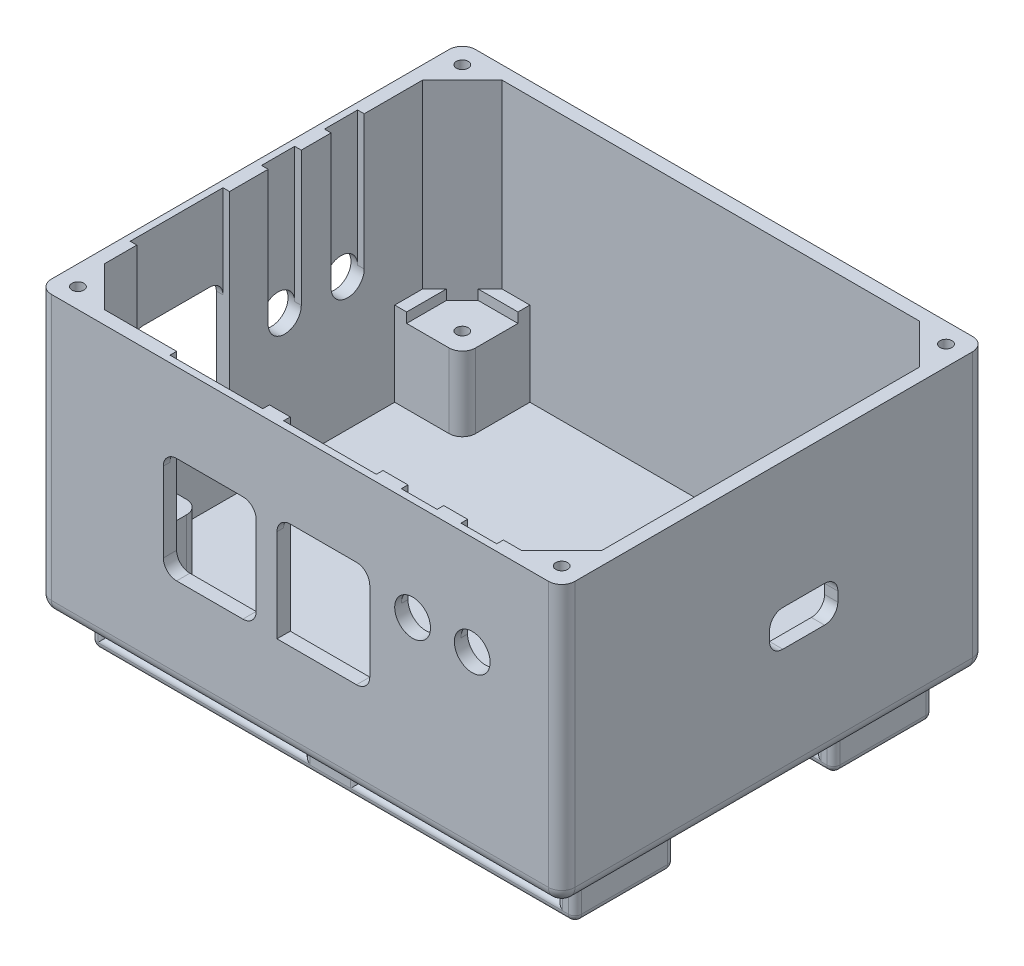
SolidWorks part; units mm, degrees
ref_plane "Front Plane" through (0, 0, 0) normal (0, 0, 1) x (1, 0, 0)
ref_plane "Top Plane" through (0, 0, 0) normal (0, 1, 0) x (1, 0, 0)
ref_plane "Right Plane" through (0, 0, 0) normal (1, 0, 0) x (0, 0, -1)
sketch "Sketch1" plane through (0, 0, 0) normal (0, 1, 0) x (1, 0, 0)
  line L1 (39.5, -32) -> (-39.5, -32)
  line L2 (39.5, -32) -> (39.5, 32)
  line L3 (39.5, 32) -> (-39.5, 32)
  line L4 (-39.5, -32) -> (-39.5, 32)
  line L5 (39.5, -32) -> (-39.5, 32) construction
  line L6 (39.5, 32) -> (-39.5, -32) construction
  point P0 (0, 0)
  dimension "D1" = 79
  dimension "D2" = 64
extrude "Boss-Extrude1" add sketch "Sketch1" along normal blind 2
sketch "Sketch2" plane through (0, 2, 0) normal (0, 1, 0) x (1, 0, 0)
  line L1 (-39.5, 32) -> (39.5, 32)
  line L2 (-39.5, 32) -> (-39.5, -32)
  line L3 (-39.5, -32) -> (39.5, -32)
  line L4 (39.5, 32) -> (39.5, -32)
  line L10 (37.5, -30) -> (-37.5, -30)
  line L14 (37.5, -30) -> (37.5, 30)
  line L15 (37.5, 30) -> (-37.5, 30)
  line L16 (-37.5, -30) -> (-37.5, 30)
  line L17 (37.5, -30) -> (-37.5, 30) construction
  line L18 (37.5, 30) -> (-37.5, -30) construction
  point P6 (0, 0)
  point P7 (0, 0)
  dimension "D1" = 2
  dimension "D2" = 2
extrude "Boss-Extrude2" add sketch "Sketch2" along normal blind 40
sketch "Sketch4" plane through (0, 2, 0) normal (0, 1, 0) x (1, 0, 0)
  line L0 (-37.5, 24) -> (-31.5, 30)
  line L1 (-37.5, 30) -> (-31.5, 30)
  line L2 (-37.5, 30) -> (-37.5, 24)
  line L5 (0, 0) -> (0, 30) construction
  line L6 (37.5, 30) -> (-37.5, 30) construction
  line L10 (0, 0) -> (-37.5, 0) construction
  line L11 (-37.5, 30) -> (-37.5, -30) construction
  line L12 (-37.5, -30) -> (-34.1667, -27.3333) construction
  line L13 (37.5, 30) -> (37.5, 24)
  line L14 (37.5, 30) -> (31.5, 30)
  line L15 (37.5, 24) -> (31.5, 30)
  line L16 (-37.5, -30) -> (-37.5, -24)
  line L17 (-37.5, -30) -> (-31.5, -30)
  line L18 (-37.5, -24) -> (-31.5, -30)
  line L19 (37.5, -30) -> (31.5, -30)
  line L20 (37.5, -24) -> (31.5, -30)
  line L21 (37.5, -30) -> (37.5, -24)
  dimension "D1" = 6
  dimension "D2" = 6
extrude "Boss-Extrude3" add sketch "Sketch4" along normal up to surface (40 mm away) up to face at (0, 42, 0)
sketch "Sketch3" plane through (0, 42, 0) normal (0, 1, 0) x (1, 0, 0)
  line L0 (39.5, 32) -> (-39.5, 32) construction
  line L1 (-39.5, 32) -> (-39.5, -32) construction
  line L3 (-39.5, -32) -> (39.5, -32) construction
  line L4 (39.5, -32) -> (39.5, 32) construction
  circle A0 centre (-36.5, 29) radius 0.9
  circle A1 centre (-36.5, -29) radius 0.9
  circle A2 centre (36.5, -29) radius 0.9
  circle A3 centre (36.5, 29) radius 0.9
  dimension "D1" = 1.8
  dimension "D2" = 3
  dimension "D3" = 3
  dimension "D4" = 1.8
  dimension "D5" = 3
  dimension "D6" = 3
  dimension "D7" = 1.8
  dimension "D8" = 3
  dimension "D9" = 3
  dimension "D10" = 1.8
  dimension "D11" = 3
  dimension "D12" = 3
extrude "Cut-Extrude2" cut sketch "Sketch3" against normal blind 10
sketch "Sketch5" plane through (0, 42, 0) normal (0, 1, 0) x (1, 0, 0)
  line L0 (-31.5, -30) -> (31.5, -30) construction
  line L1 (-20.6111, -30) -> (-6.6111, -30)
  line L2 (-20.6111, -30) -> (-20.6111, -31)
  line L3 (-20.6111, -31) -> (-6.6111, -31)
  line L4 (-6.6111, -30) -> (-6.6111, -31)
  line L5 (-37.5, 24) -> (-37.5, -24) construction
  line L6 (-3.4629, -30) -> (10.5371, -30)
  line L7 (-3.4629, -30) -> (-3.4629, -31)
  line L8 (-3.4629, -31) -> (10.5371, -31)
  line L9 (10.5371, -30) -> (10.5371, -31)
  line L10 (-37.5, -5.1206) -> (-38.5, -5.1206)
  line L11 (-37.5, -5.1206) -> (-37.5, -19.1206)
  line L12 (-37.5, -19.1206) -> (-38.5, -19.1206)
  line L13 (-38.5, -5.1206) -> (-38.5, -19.1206)
  dimension "D1" = 14
  dimension "D2" = 14
  dimension "D3" = 1
  dimension "D4" = 1
  dimension "D5" = 14
  dimension "D6" = 1
extrude "Cut-Extrude3" cut sketch "Sketch5" against normal blind 28
sketch "Sketch6" plane through (0, 0, 31) normal (0, 0, -1) x (-1, 0, 0)
  line L0 (6.6111, 14) -> (6.6111, 42) construction
  line L1 (20.6111, 14) -> (6.6111, 14)
  line L2 (20.6111, 14) -> (20.6111, 30)
  line L3 (20.6111, 30) -> (6.6111, 30)
  line L4 (6.6111, 14) -> (6.6111, 30)
  line L5 (3.4629, 14) -> (3.4629, 42) construction
  line L6 (-10.5371, 14) -> (3.4629, 14)
  line L7 (-10.5371, 14) -> (-10.5371, 30)
  line L8 (-10.5371, 30) -> (3.4629, 30)
  line L9 (3.4629, 14) -> (3.4629, 30)
  dimension "D1" = 16
  dimension "D2" = 16
extrude "Cut-Extrude4" cut sketch "Sketch6" against normal blind 2
sketch "Sketch7" plane through (-38.5, 0, 0) normal (1, 0, 0) x (0, 0, -1)
  line L0 (-19.1206, 14) -> (-19.1206, 42) construction
  line L1 (-5.1206, 14) -> (-19.1206, 14)
  line L2 (-5.1206, 14) -> (-5.1206, 30)
  line L3 (-5.1206, 30) -> (-19.1206, 30)
  line L4 (-19.1206, 14) -> (-19.1206, 30)
  dimension "D1" = 16
extrude "Cut-Extrude5" cut sketch "Sketch7" against normal blind 2
sketch "Sketch8" plane through (0, 42, 0) normal (0, 1, 0) x (1, 0, 0)
  line L0 (-37.5, 24) -> (-37.5, -5.1206) construction
  line L1 (-37.5, 15.4397) -> (-38.5, 15.4397)
  line L2 (-37.5, 15.4397) -> (-37.5, 9.4397)
  line L3 (-37.5, 9.4397) -> (-38.5, 9.4397)
  line L4 (-38.5, 15.4397) -> (-38.5, 9.4397)
  line L6 (-37.5, 6) -> (-38.5, 6)
  line L7 (-37.5, 6) -> (-37.5, 0)
  line L8 (-37.5, 0) -> (-38.5, 0)
  line L9 (-38.5, 6) -> (-38.5, 0)
  dimension "D1" = 6
  dimension "D2" = 6
  dimension "D3" = 1
  dimension "D4" = 1
sketch "Sketch9" plane through (-37.5, 0, 0) normal (1, 0, 0) x (0, 0, -1)
  line L0 (24, 42) -> (-5.1206, 42) construction
  line L1 (24, 42) -> (24, 2) construction
  line L2 (15.4397, 42) -> (9.4397, 42) construction
  line L4 (0.7, 21.71) -> (0.7, 42)
  line L5 (0.7, 42) -> (5.7, 42)
  line L6 (5.7, 21.71) -> (5.7, 42)
  line L8 (10.2, 21.71) -> (10.2, 42)
  line L9 (10.2, 42) -> (15.2, 42)
  line L10 (15.2, 21.71) -> (15.2, 42)
  arc A0 (10.2, 21.71) -> (15.2, 21.71) centre (12.7, 21.71) ccw
  arc A1 (0.7, 21.71) -> (5.7, 21.71) centre (3.2, 21.71) ccw
  dimension "D1" = 5
  dimension "D2" = 5
  dimension "D3" = 20.29
  dimension "D4" = 20.29
  dimension "D6" = 11.3
  dimension "D5" = 9.5
extrude "Cut-Extrude7" cut sketch "Sketch9" against normal blind 1
sketch "Sketch10" plane through (-38.5, 0, 0) normal (1, 0, 0) x (0, 0, -1)
  circle A0 centre (3.2, 21.71) radius 2.5
  circle A1 centre (12.7, 21.71) radius 2.5
extrude "Cut-Extrude8" cut sketch "Sketch10" against normal blind 3
sketch "Sketch11" plane through (0, 0, 32) normal (0, 0, 1) x (1, 0, 0)
  line L0 (-39.5, 42) -> (39.5, 42) construction
  line L1 (39.5, 42) -> (39.5, 0) construction
  circle A0 centre (17, 27) radius 2.7
  circle A2 centre (26, 27) radius 2.7
  dimension "D1" = 5.4
  dimension "D2" = 5.4
  dimension "D3" = 15
  dimension "D4" = 15
  dimension "D5" = 9
  dimension "D6" = 13.5
extrude "Cut-Extrude9" cut sketch "Sketch11" against normal blind 3
sketch "Sketch12" plane through (0, 0, 30) normal (0, 0, -1) x (-1, 0, 0)
  line L0 (-10.5371, 42) -> (-31.5, 42) construction
  line L1 (-28.7, 27) -> (-23.3, 27)
  line L2 (-28.7, 27) -> (-28.7, 42)
  line L3 (-28.7, 42) -> (-23.3, 42)
  line L4 (-23.3, 27) -> (-23.3, 42)
  line L6 (-19.7, 27) -> (-14.3, 27)
  line L7 (-19.7, 27) -> (-19.7, 42)
  line L8 (-19.7, 42) -> (-14.3, 42)
  line L9 (-14.3, 27) -> (-14.3, 42)
  circle A0 centre (-26, 27) radius 2.7 construction
  circle A1 centre (-17, 27) radius 2.7 construction
extrude "Cut-Extrude10" cut sketch "Sketch12" against normal blind 1
sketch "Sketch13" plane through (37.5, 0, 0) normal (-1, 0, 0) x (0, 0, 1)
  line L0 (24, 2) -> (-24, 2) construction
  line L1 (-9.67, 22.89) -> (0.63, 22.89)
  line L2 (-9.67, 22.89) -> (-9.67, 17.44)
  line L3 (-9.67, 17.44) -> (0.63, 17.44)
  line L4 (0.63, 22.89) -> (0.63, 17.44)
  line L5 (-32, 42) -> (-32, 0) construction
  dimension "D1" = 5.45
  dimension "D2" = 10.3
  dimension "D3" = 15.44
  dimension "D4" = 22.33
extrude "Cut-Extrude11" cut sketch "Sketch13" against normal blind 2
fillet "Fillet1" radius 2 3 edges at (-39.5, 0, 0) (-39.5, 21, -32) (-39.5, 21, 32)
fillet "Fillet2" radius 2 3 edges at (39.5, 0, 0) (39.5, 21, -32) (39.5, 21, 32)
fillet "Fillet3" radius 2 3 edges at (-38.9142, 0.5858, -31.4142) (0, 0, -32) (38.9142, 0.5858, -31.4142)
fillet "Fillet4" radius 2 3 edges at (0, 0, 32) (-38.9142, 0.5858, 31.4142) (38.9142, 0.5858, 31.4142)
fillet "Fillet5" radius 2 1 edges at (-20.6111, 14, 31)
fillet "Fillet6" radius 2 1 edges at (-6.6111, 30, 31.5)
fillet "Fillet7" radius 2 1 edges at (-20.6111, 30, 31.5)
fillet "Fillet8" radius 2 1 edges at (-6.6111, 14, 31)
fillet "Fillet9" radius 2 1 edges at (-3.4629, 30, 31.5)
fillet "Fillet10" radius 2 1 edges at (10.5371, 30, 31.5)
fillet "Fillet11" radius 2 1 edges at (10.5371, 14, 31)
fillet "Fillet12" radius 2 1 edges at (-38.5, 14, 5.1206)
fillet "Fillet13" radius 2 1 edges at (-38.5, 14, 19.1206)
fillet "Fillet14" radius 2 1 edges at (-39, 30, 19.1206)
fillet "Fillet15" radius 2 1 edges at (-39, 30, 5.1206)
fillet "Fillet16" radius 2 1 edges at (38.5, 17.44, -9.67)
fillet "Fillet17" radius 2 1 edges at (38.5, 22.89, 0.63)
fillet "Fillet18" radius 2 1 edges at (38.5, 22.89, -9.67)
fillet "Fillet19" radius 2 1 edges at (38.5, 17.44, 0.63)
sketch "Sketch14" plane through (0, 2, 0) normal (0, 1, 0) x (1, 0, 0)
  line L0 (-31.5, -30) -> (31.5, -30) construction
  line L1 (-27.3, -30) -> (-37.5, -30)
  line L2 (-27.3, -30) -> (-27.3, -19.8)
  line L3 (-27.3, -19.8) -> (-37.5, -19.8)
  line L4 (-37.5, -30) -> (-37.5, -19.8)
  line L5 (-37.5, 24) -> (-37.5, -24) construction
  line L6 (31.5, 30) -> (-31.5, 30) construction
  line L7 (-37.5, 19.8) -> (-27.3, 19.8)
  line L8 (-37.5, 19.8) -> (-37.5, 30)
  line L9 (-37.5, 30) -> (-27.3, 30)
  line L10 (-27.3, 19.8) -> (-27.3, 30)
  line L11 (37.5, -24) -> (37.5, 24) construction
  line L12 (28.3, -30) -> (37.5, -30)
  line L13 (28.3, -30) -> (28.3, -19.8)
  line L14 (28.3, -19.8) -> (37.5, -19.8)
  line L15 (37.5, -30) -> (37.5, -19.8)
  line L17 (28.3, 30) -> (37.5, 30)
  line L18 (28.3, 30) -> (28.3, 19.8)
  line L19 (28.3, 19.8) -> (37.5, 19.8)
  line L20 (37.5, 30) -> (37.5, 19.8)
  dimension "D1" = 10.2
  dimension "D2" = 10.2
  dimension "D3" = 10.2
  dimension "D4" = 10.2
  dimension "D5" = 10.2
  dimension "D6" = 9.2
  dimension "D7" = 9.2
  dimension "D8" = 10.2
extrude "Boss-Extrude5" add sketch "Sketch14" along normal blind 11.2
sketch "Sketch15" plane through (0, 13.2, 0) normal (0, 1, 0) x (1, 0, 0)
  line L0 (37.5, -24) -> (37.5, -19.8) construction
  line L1 (28.3, -30) -> (31.5, -30) construction
  line L2 (37.5, 19.8) -> (37.5, 24) construction
  line L3 (31.5, 30) -> (28.3, 30) construction
  line L4 (-37.5, -19.8) -> (-37.5, -24) construction
  line L5 (-31.5, -30) -> (-27.3, -30) construction
  line L6 (-27.3, 30) -> (-31.5, 30) construction
  line L7 (-37.5, 24) -> (-37.5, 19.8) construction
  circle A0 centre (-30.5, -23) radius 0.9
  circle A1 centre (-30.5, 23) radius 0.9
  circle A2 centre (31.5, 23) radius 0.9
  circle A3 centre (31.5, -23) radius 0.9
  dimension "D1" = 1.8
  dimension "D2" = 1.8
  dimension "D3" = 1.8
  dimension "D4" = 1.8
  dimension "D5" = 6
  dimension "D6" = 7
  dimension "D7" = 6
  dimension "D8" = 7
  dimension "D9" = 7
  dimension "D10" = 7
  dimension "D11" = 7
  dimension "D12" = 7
extrude "Cut-Extrude12" cut sketch "Sketch15" against normal blind 10
sketch "Sketch17" plane through (0, 13.2, 0) normal (0, 1, 0) x (1, 0, 0)
  line L0 (-37.5, 24) -> (-35.7, 25.8)
  line L1 (-37.5, -19.8) -> (-35.7, -19.8)
  line L2 (-37.5, -19.8) -> (-37.5, -24)
  line L4 (-35.7, -19.8) -> (-35.7, -25.8)
  line L5 (-27.3, -30) -> (-31.5, -30)
  line L6 (-27.3, -30) -> (-27.3, -28.2)
  line L7 (-27.3, -28.2) -> (-33.3, -28.2)
  line L9 (-37.5, 19.8) -> (-35.7, 19.8)
  line L10 (-37.5, 19.8) -> (-37.5, 24)
  line L12 (-35.7, 19.8) -> (-35.7, 25.8)
  line L13 (-27.3, 30) -> (-31.5, 30)
  line L14 (-27.3, 30) -> (-27.3, 28.2)
  line L15 (-27.3, 28.2) -> (-33.3, 28.2)
  line L17 (37.5, 19.8) -> (36.7, 19.8)
  line L18 (37.5, 19.8) -> (37.5, 24)
  line L20 (36.7, 19.8) -> (36.7, 24.8)
  line L21 (28.3, 30) -> (31.5, 30)
  line L22 (28.3, 30) -> (28.3, 28.2)
  line L23 (28.3, 28.2) -> (33.3, 28.2)
  line L25 (28.3, -30) -> (31.5, -30)
  line L26 (28.3, -30) -> (28.3, -28.2)
  line L27 (28.3, -28.2) -> (33.3, -28.2)
  line L29 (37.5, -19.8) -> (36.7, -19.8)
  line L30 (37.5, -19.8) -> (37.5, -24)
  line L32 (36.7, -19.8) -> (36.7, -24.8)
  line L33 (-31.5, -30) -> (-33.3, -28.2)
  line L34 (31.5, -30) -> (33.3, -28.2)
  line L35 (31.5, 30) -> (33.3, 28.2)
  line L36 (-35.7, -25.8) -> (-37.5, -24)
  line L37 (-33.3, 28.2) -> (-31.5, 30)
  line L38 (36.7, 24.8) -> (37.5, 24)
  line L39 (36.7, -24.8) -> (37.5, -24)
  dimension "D1" = 0.8
  dimension "D2" = 1.8
  dimension "D3" = 0.8
  dimension "D4" = 1.8
  dimension "D5" = 1.8
  dimension "D6" = 1.8
  dimension "D7" = 1.8
  dimension "D8" = 1.8
extrude "Boss-Extrude6" add sketch "Sketch17" along normal blind 1.5
fillet "Fillet20" radius 2 1 edges at (-27.3, 7.6, 19.8)
fillet "Fillet21" radius 2 1 edges at (-27.3, 7.6, -19.8)
fillet "Fillet22" radius 2 1 edges at (28.3, 7.6, -19.8)
fillet "Fillet23" radius 2 1 edges at (28.3, 7.6, 19.8)
sketch "Sketch18" plane through (0, 0, 0) normal (0, -1, 0) x (1, 0, 0)
  line L0 (-39.5, -30) -> (-39.5, 30) construction
  line L1 (-36.5, 27) -> (-2.5, 27)
  line L2 (-36.5, 27) -> (-36.5, 12)
  line L3 (-36.5, 12) -> (-2.5, 12)
  line L5 (2.5, 27) -> (36.5, 27)
  line L7 (2.5, 12) -> (36.5, 12)
  line L8 (36.5, 27) -> (36.5, 12)
  line L9 (39.5, 30) -> (39.5, -30) construction
  line L10 (-37.5, 32) -> (37.5, 32) construction
  line L11 (37.5, -32) -> (-37.5, -32) construction
  line L12 (-36.5, -12) -> (-2.5, -12)
  line L13 (-36.5, -12) -> (-36.5, -27)
  line L14 (-36.5, -27) -> (-2.5, -27)
  line L16 (2.5, -12) -> (36.5, -12)
  line L18 (2.5, -27) -> (36.5, -27)
  line L19 (36.5, -12) -> (36.5, -27)
  line L20 (-2.5, 27) -> (2.5, 27)
  line L21 (-2.5, 12) -> (2.5, 12)
  line L22 (-2.5, -12) -> (2.5, -12)
  line L23 (-2.5, -27) -> (2.5, -27)
  dimension "D1" = 34
  dimension "D2" = 34
  dimension "D3" = 3
  dimension "D4" = 3
  dimension "D5" = 15
  dimension "D6" = 15
  dimension "D7" = 5
  dimension "D8" = 5
  dimension "D9" = 34
  dimension "D10" = 34
  dimension "D11" = 15
  dimension "D12" = 15
  dimension "D13" = 5
  dimension "D14" = 5
extrude "Boss-Extrude7" add sketch "Sketch18" along normal blind 6
sketch "Sketch20" plane through (0, 0, -27) normal (0, 0, -1) x (-1, 0, 0)
  line L0 (36.5, 0) -> (-36.5, 0) construction
  line L1 (34.5, 0) -> (4.5, 0)
  line L2 (34.5, 0) -> (34.5, -4)
  line L3 (34.5, -4) -> (4.5, -4)
  line L4 (4.5, 0) -> (4.5, -4)
  line L5 (36.5, -6) -> (-36.5, -6) construction
  line L6 (-3.628, 0) -> (-33.628, 0)
  line L7 (-3.628, 0) -> (-3.628, -4)
  line L8 (-3.628, -4) -> (-33.628, -4)
  line L9 (-33.628, 0) -> (-33.628, -4)
  line L10 (-36.5, -6) -> (-36.5, 0) construction
  line L11 (36.5, -6) -> (36.5, 0) construction
  dimension "D1" = 2
  dimension "D2" = 2.872
  dimension "D3" = 2
  dimension "D4" = 2
  dimension "D5" = 30
  dimension "D6" = 30
extrude "Cut-Extrude13" cut sketch "Sketch20" against normal blind 58
fillet "Fillet37" radius 1 28 edges at (-4.5, 0, 19.5) (3.628, 0, 19.5) (33.628, 0, 19.5) (36.5, 0, 19.5) (-36.5, 0, 19.5) (-34.5, 0, 19.5) (-4.5, -2, 27) (-0.436, 0, 27) (3.628, -2, 27) (18.628, -4, 27) (33.628, -2, 27) (35.064, 0, 27) (36.5, -3, 27) (0, -6, 27) (-36.5, -3, 27) (-34.5, -2, 27) (-19.5, -4, 27) (-36.5, -3, 12) (0, -6, 12) (36.5, -3, 12) (35.064, 0, 12) (33.628, -2, 12) (18.628, -4, 12) (3.628, -2, 12) (-0.436, 0, 12) (-4.5, -2, 12) (-19.5, -4, 12) (-34.5, -2, 12)
fillet "Fillet39" radius 1 28 edges at (-4.5, 0, -19.5) (3.628, 0, -19.5) (33.628, 0, -19.5) (36.5, 0, -19.5) (-36.5, 0, -19.5) (-34.5, 0, -19.5) (-36.5, -3, -27) (0, -6, -27) (36.5, -3, -27) (35.064, 0, -27) (33.628, -2, -27) (18.628, -4, -27) (3.628, -2, -27) (-0.436, 0, -27) (-4.5, -2, -27) (-19.5, -4, -27) (-34.5, -2, -27) (-4.5, -2, -12) (-0.436, 0, -12) (3.628, -2, -12) (18.628, -4, -12) (33.628, -2, -12) (35.064, 0, -12) (36.5, -3, -12) (0, -6, -12) (-36.5, -3, -12) (-34.5, -2, -12) (-19.5, -4, -12)
fillet "Fillet42" radius 1 3 edges at (36.5, -6, 19.5) (36.2071, -5.7071, 26.7071) (36.2071, -5.7071, 12.2929)
fillet "Fillet43" radius 1 3 edges at (-36.5, -6, 19.5) (-36.2071, -5.7071, 26.7071) (-36.2071, -5.7071, 12.2929)
fillet "Fillet44" radius 1 3 edges at (-36.5, -6, -19.5) (-36.2071, -5.7071, -12.2929) (-36.2071, -5.7071, -26.7071)
fillet "Fillet45" radius 1 3 edges at (36.5, -6, -19.5) (36.2071, -5.7071, -12.2929) (36.2071, -5.7071, -26.7071)
equation "\"esquina\"= 8"
